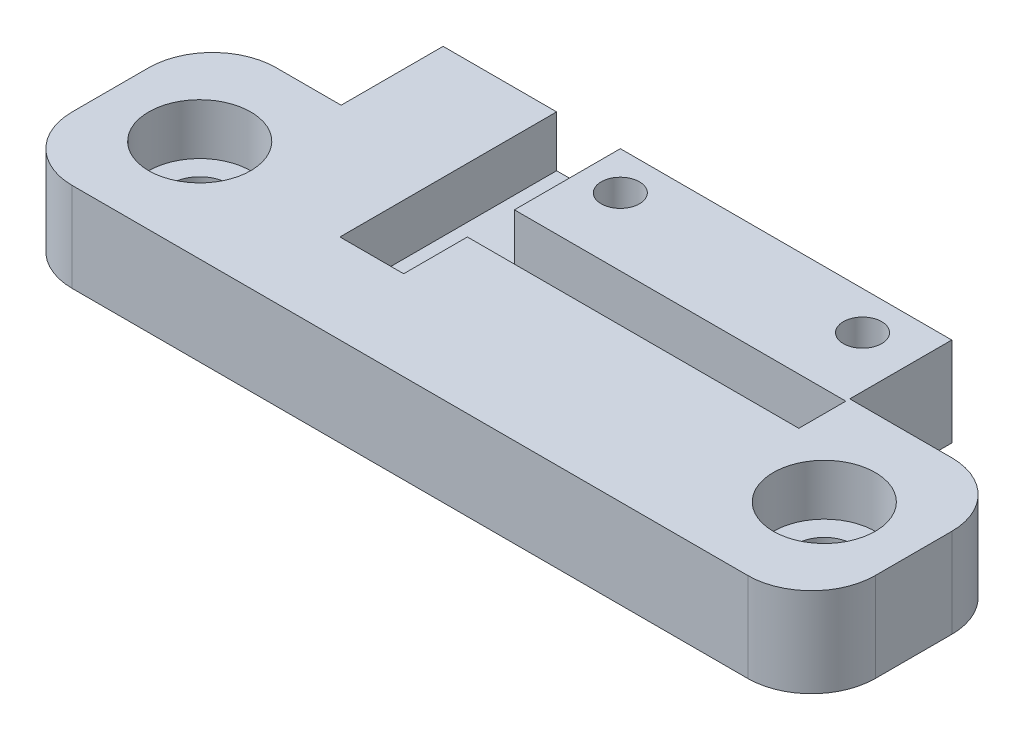
SolidWorks part; units mm, degrees
ref_plane "Спереди" through (0, 0, 0) normal (0, 0, 1) x (1, 0, 0)
ref_plane "Сверху" through (0, 0, 0) normal (0, 1, 0) x (1, 0, 0)
ref_plane "Справа" through (0, 0, 0) normal (1, 0, 0) x (0, 0, -1)
sketch "Эскиз1" plane through (0, 0, 0) normal (0, 1, 0) x (1, 0, 0)
  line L1 (0, 0) -> (63, 0)
  line L2 (0, 0) -> (0, 16)
  line L3 (0, 16) -> (63, 16)
  line L4 (63, 0) -> (63, 16)
  line L5 (50, 16) -> (10.0954, 16)
  line L6 (50, 16) -> (50, 24)
  line L7 (50, 24) -> (10.0954, 24)
  line L8 (10.0954, 16) -> (10.0954, 24)
  dimension "D1" = 16
  dimension "D2" = 63
extrude "Бобышка-Вытянуть1" add sketch "Эскиз1" along normal blind 7 contours L1 L4 L3 L2 | L8 L3 L6 L7 region at (31.5, 0, -8) region at (30.0477, 0, -20)
sketch "Эскиз2" plane through (0, 0, 0) normal (0, 1, 0) x (1, 0, 0)
  line L2 (0, 0) -> (0, 16) construction
  line L3 (63, 0) -> (63, 16) construction
  circle A0 centre (7, 8) radius 2.25
  circle A1 centre (56, 8) radius 2.25
  point P12 (63, 8)
  dimension "D1" = 4.5
  dimension "D2" = 7
  dimension "D3" = 7
extrude "Вырез-Вытянуть1" cut sketch "Эскиз2" along normal blind 47 contours A0 | A1 region at (7, 0, -8) region at (56, 0, -8)
sketch "Эскиз3" plane through (0, 0, 0) normal (0, -1, 0) x (1, 0, 0)
  line L0 (63, 0) -> (63, -16) construction
  line L1 (48, -5) -> (15, -5)
  line L2 (48, -5) -> (48, -11)
  line L3 (48, -11) -> (15, -11)
  line L4 (15, -5) -> (15, -11)
  point P4 (48, -8)
  point P9 (63, -8)
  dimension "D1" = 6
extrude "Бобышка-Вытянуть2" add sketch "Эскиз3" along normal blind 4
sketch "Эскиз5" plane through (0, 7, 0) normal (0, 1, 0) x (1, 0, 0)
  line L1 (50, 15.69) -> (24, 15.69)
  line L2 (50, 15.69) -> (50, 12)
  line L3 (50, 12) -> (24, 12)
  line L4 (24, 15.69) -> (24, 12)
  line L5 (24, 7) -> (19, 7)
  line L6 (24, 7) -> (24, 33.2091)
  line L7 (24, 33.2091) -> (19, 33.2091)
  line L8 (19, 7) -> (19, 33.2091)
  line L9 (50, 15.69) -> (24, 15.69) construction
  line L11 (24, 24) -> (24, 15.69) construction
  circle A0 centre (46, 21) radius 1.5 construction
  circle A1 centre (46, 21) radius 1.5
  circle A2 centre (27, 21) radius 1.5 construction
  circle A3 centre (27, 21) radius 1.5
  line M19 (50, 24) -> (10.0954, 24)
extrude "Вырез-Вытянуть2" cut sketch "Эскиз5" against normal blind 4 contours L1 L4 L3 L2 | L8 L5 L6 L4 M19 region at (37, 7, -13.845) region at (21.5, 7, -15.5)
extrude "Вырез-Вытянуть3" cut sketch "Эскиз5<3>" against normal blind 20 contours A3 | A1 region at (27, 7, -21)
sketch "Эскиз5<3>" plane through (0, 7, 0) normal (0, 1, 0) x (1, 0, 0) same geometry as "Эскиз5"
sketch "Эскиз6" plane through (0, 0, 0) normal (0, -1, 0) x (1, 0, 0)
  line L1 (47.7321, -18) -> (44.2679, -18)
  line L2 (44.2679, -18) -> (42.5359, -21)
  line L3 (42.5359, -21) -> (44.2679, -24)
  line L4 (44.2679, -24) -> (47.7321, -24)
  line L5 (47.7321, -24) -> (49.4641, -21)
  line L6 (49.4641, -21) -> (47.7321, -18)
  line L7 (30.4641, -21) -> (28.7321, -18)
  line L8 (28.7321, -18) -> (25.2679, -18)
  line L9 (25.2679, -18) -> (23.5359, -21)
  line L10 (23.5359, -21) -> (25.2679, -24)
  line L11 (25.2679, -24) -> (28.7321, -24)
  line L12 (28.7321, -24) -> (30.4641, -21)
  circle A0 centre (46, -21) radius 3 construction
  circle A1 centre (27, -21) radius 3 construction
  dimension "D1" = 6
extrude "Вырез-Вытянуть4" cut sketch "Эскиз6" against normal blind 2
fillet "Скругление1" radius 5 4 edges at (0, 3.5, -16) (0, 3.5, 0) (63, 3.5, 0) (63, 3.5, -16)
sketch "Эскиз7" plane through (0, 7, 0) normal (0, 1, 0) x (1, 0, 0)
  circle A0 centre (7, 8) radius 4
  circle A1 centre (56, 8) radius 4
  circle A2 centre (56, 8) radius 2.25 construction
  circle A3 centre (7, 8) radius 2.25 construction
  dimension "D1" = 8
extrude "Вырез-Вытянуть5" cut sketch "Эскиз7" against normal blind 4
